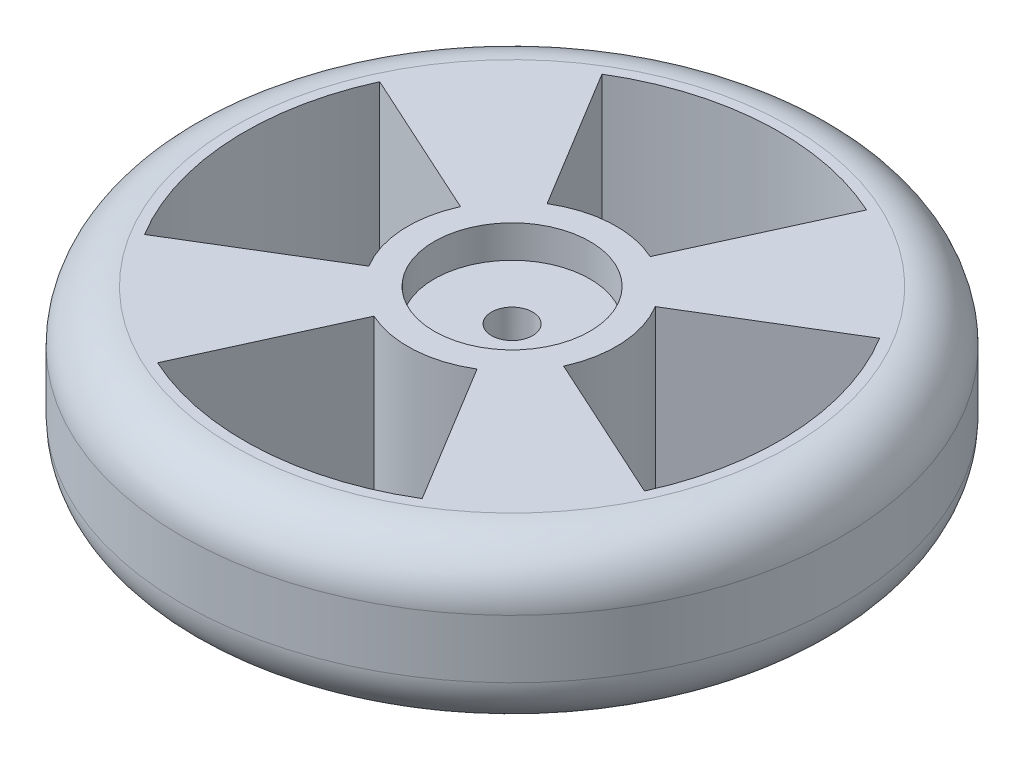
SolidWorks part; units mm, degrees
ref_plane "Front Plane" through (0, 0, 0) normal (0, 0, 1) x (1, 0, 0)
ref_plane "Top Plane" through (0, 0, 0) normal (0, 1, 0) x (1, 0, 0)
ref_plane "Right Plane" through (0, 0, 0) normal (1, 0, 0) x (0, 0, -1)
sketch "Sketch1" plane through (0, 0, 0) normal (0, 1, 0) x (1, 0, 0)
  circle A0 centre (0, 0) radius 50.8
extrude "Boss-Extrude1" add sketch "Sketch1" along normal blind 25 contours A0
fillet "Fillet2" radius 8 1 edges at (0, 25, 50.8)
fillet "Fillet3" radius 8 1 edges at (0, 0, 50.8)
sketch "Sketch2" plane through (0, 0, 0) normal (0, -1, 0) x (1, 0, 0)
  circle A0 centre (0, 0) radius 15
extrude "Boss-Extrude2" add sketch "Sketch2" along normal blind 5
sketch "Sketch3" plane through (0, 25, 0) normal (0, 1, 0) x (1, 0, 0)
  circle A0 centre (0, 0) radius 12
extrude "Cut-Extrude1" cut sketch "Sketch3" against normal blind 5
fillet "Fillet4" radius 8 1 edges at (0, 0, 15)
sketch "Sketch5" plane through (0, -5, 0) normal (0, -1, 0) x (1, 0, 0)
  line L0 (0, 8) -> (0, -7.0266) construction
  line L1 (-4.5258, 0) -> (8, 0) construction
  circle A0 centre (0, 0) radius 10.25 construction
  circle A1 centre (0, 0) radius 8 construction
  circle A6 centre (0, 0) radius 3.165
extrude "Cut-Extrude2" cut sketch "Sketch5" against normal through all
sketch "Sketch6" plane through (0, 25, 0) normal (0, 1, 0) x (1, 0, 0)
  line L0 (30.1741, -28.1197) -> (-30.1741, 28.1197) construction
  line L1 (-31.2322, -29.2642) -> (31.2322, 29.2642) construction
  line L2 (1.0285, -41.2327) -> (-1.0285, 41.2327) construction
  line L3 (41.2456, 0) -> (-41.2456, 0) construction
  line L4 (6.6696, 14.6192) -> (17.1198, 37.5248)
  line L5 (-8.3374, 13.7365) -> (-21.4007, 35.2591)
  line L6 (13.7365, 8.3374) -> (35.2591, 21.4007)
  line L7 (14.6192, -6.6696) -> (37.5248, -17.1198)
  line L8 (8.3374, -13.7365) -> (21.4007, -35.2591)
  line L9 (-6.6696, -14.6192) -> (-17.1198, -37.5248)
  line L10 (-13.7365, -8.3374) -> (-35.2591, -21.4007)
  line L11 (-14.6192, 6.6696) -> (-37.5248, 17.1198)
  circle A0 centre (0, 0) radius 16.0687 construction
  circle A2 centre (0, 0) radius 41.2456 construction
  arc A3 (6.6696, 14.6192) -> (-8.3374, 13.7365) centre (0, 0) ccw
  circle A4 centre (0, 0) radius 42.8 construction
  arc A5 (17.1198, 37.5248) -> (-21.4007, 35.2591) centre (0, 0) ccw
  arc A6 (37.5248, -17.1198) -> (35.2591, 21.4007) centre (0, 0) ccw
  arc A7 (14.6192, -6.6696) -> (13.7365, 8.3374) centre (0, 0) ccw
  arc A8 (-17.1198, -37.5248) -> (21.4007, -35.2591) centre (0, 0) ccw
  arc A9 (-6.6696, -14.6192) -> (8.3374, -13.7365) centre (0, 0) ccw
  arc A10 (-37.5248, 17.1198) -> (-35.2591, -21.4007) centre (0, 0) ccw
  arc A11 (-14.6192, 6.6696) -> (-13.7365, -8.3374) centre (0, 0) ccw
  point P13 (0, 0)
  point P14 (0, 0)
  point P18 (0, 0)
  point P20 (0, 0)
  point P21 (0, 0)
  point P37 (0, 0)
  dimension "D1" = 4
extrude "Cut-Extrude3" cut sketch "Sketch6" against normal through all
